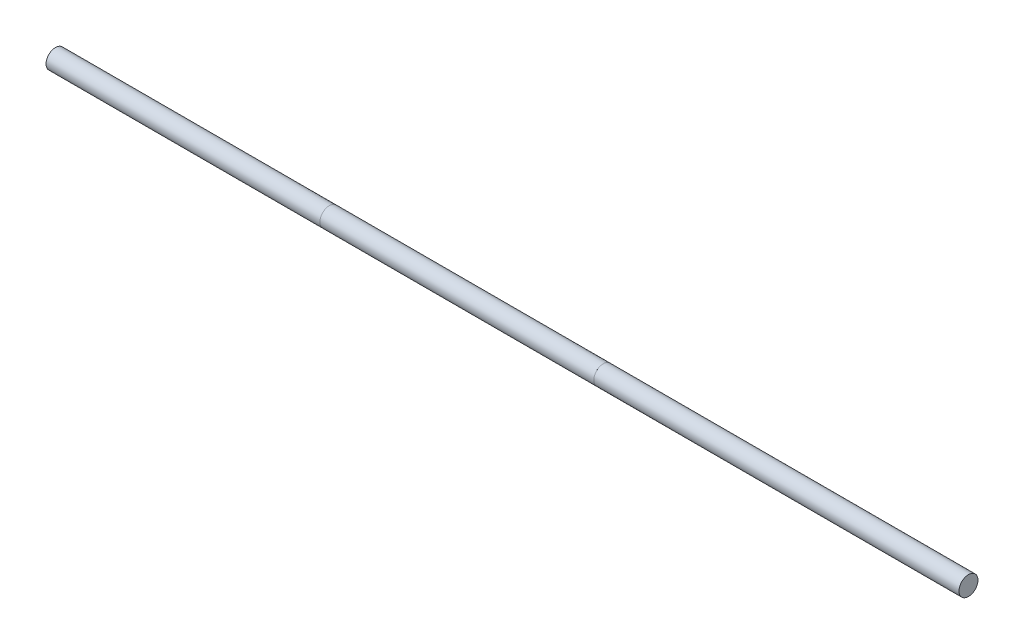
SolidWorks part; units mm, degrees
material "Alloy Steel"
ref_plane "Front Plane" through (0, 0, 0) normal (0, 0, 1) x (1, 0, 0)
ref_plane "Top Plane" through (0, 0, 0) normal (0, 1, 0) x (1, 0, 0)
ref_plane "Right Plane" through (0, 0, 0) normal (1, 0, 0) x (0, 0, -1)
sketch "Sketch1" plane through (0, 0, 0) normal (0, 0, 1) x (1, 0, 0)
  line L0 (0, 0) -> (914.4, 0)
  line L1 (914.4, 0) -> (1828.8, 0)
  line L2 (1828.8, 0) -> (3048, 0)
  point P5 (0, 0)
  point P6 (0, 0)
  point P7 (0, 0)
  point P8 (0, 0)
  point P9 (0, 0)
  point P10 (0, 0)
  point P11 (0, 0)
  point P12 (0, 0)
  dimension "D1" = 914.4
  dimension "D2" = 914.4
  dimension "D3" = 1219.2
sketch "Sketch2" plane through (0, 0, 0) normal (1, 0, 0) x (0, 0, -1)
  circle A0 centre (0, 0) radius 31.75
  point P2 (-16.0475, 3.6662)
  dimension "D1" = 63.5
extrude "Boss-Extrude1" add sketch "Sketch2" along normal up to vertex (914.4 mm away) up to point (914.4, 0, 0)
extrude "Boss-Extrude2" add sketch "Sketch2<2>" along normal up to vertex (1828.8 mm away) from vertex separate body up to point (1828.8, 0, 0) starting at point (914.4, 0, 0)
sketch "Sketch2<2>" plane through (0, 0, 0) normal (1, 0, 0) x (0, 0, -1) same geometry as "Sketch2"
extrude "Boss-Extrude3" add sketch "Sketch2<3>" along normal up to vertex (3048 mm away) from vertex separate body up to point (3048, 0, 0) starting at point (1828.8, 0, 0)
sketch "Sketch2<3>" plane through (0, 0, 0) normal (1, 0, 0) x (0, 0, -1) same geometry as "Sketch2"
